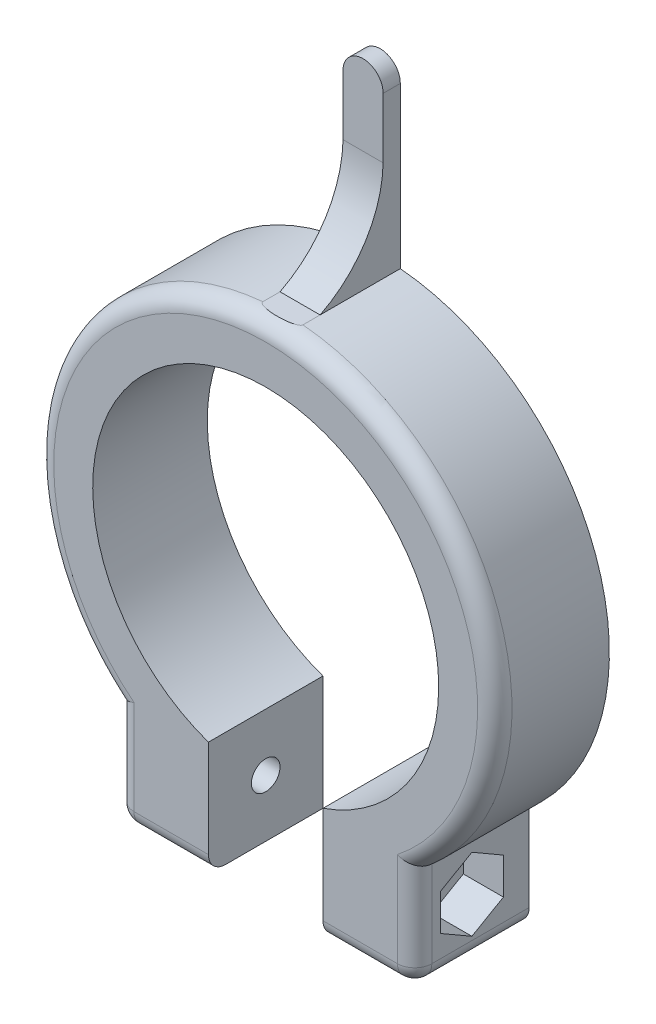
SolidWorks part; units mm, degrees
ref_plane "Front Plane" through (0, 0, 0) normal (0, 0, 1) x (1, 0, 0)
ref_plane "Top Plane" through (0, 0, 0) normal (0, 1, 0) x (1, 0, 0)
ref_plane "Right Plane" through (0, 0, 0) normal (1, 0, 0) x (0, 0, -1)
sketch "Sketch1" plane through (0, 0, 0) normal (0, 0, 1) x (1, 0, 0)
  line L0 (-5, -14.2482) -> (-5, -24.2482)
  line L1 (5, -14.2482) -> (5, -24.2482)
  line L2 (-5, -24.2482) -> (-13, -24.2482)
  line L3 (5, -24.2482) -> (13, -24.2482)
  line L4 (-13, -24.2482) -> (-13, -15.1987)
  line L5 (13, -24.2482) -> (13, -15.1987)
  line L6 (-1.75, 19.9233) -> (-1.75, 33.9233)
  line L7 (1.75, 19.9233) -> (1.75, 33.9233)
  arc A0 (5, -14.2482) -> (-5, -14.2482) centre (0, 0) ccw
  arc A1 (13, -15.1987) -> (1.75, 19.9233) centre (0, 0) ccw
  arc A2 (-1.75, 19.9233) -> (-13, -15.1987) centre (0, 0) ccw
  arc A3 (1.75, 33.9233) -> (-1.75, 33.9233) centre (0, 33.9233) ccw
  dimension "D1" = 30.2
  dimension "D2" = 40
  dimension "D13" = 1.75
  dimension "D3" = 5
  dimension "D4" = 5
  dimension "D5" = 10
  dimension "D6" = 10
  dimension "D7" = 8
  dimension "D8" = 8
  dimension "D9" = 1.75
  dimension "D10" = 1.75
  dimension "D11" = 14
  dimension "D12" = 14
extrude "Boss-Extrude1" add sketch "Sketch1" along normal blind 10
sketch "Sketch2" plane through (0, 0, 0) normal (1, 0, 0) x (0, 0, -1)
  line L0 (-10, 19.9233) -> (-7, 19.9233)
  line L1 (-10, 19.9233) -> (0, 19.9233) construction
  line L3 (-10, 35.6733) -> (-1.5, 35.6733)
  line L4 (0, 35.6733) -> (-10, 35.6733) construction
  line L5 (-10, 35.6733) -> (-10, 19.9233)
  line L6 (-1.5, 35.6733) -> (-1.5, 28.6733)
  line L7 (0, 33.9233) -> (0, 35.6733) construction
  arc A0 (-7, 19.9233) -> (-1.5, 28.6733) centre (-11.4984, 28.8544) ccw
  dimension "D4" = 10
  dimension "D1" = 1.5
  dimension "D2" = 7
  dimension "D3" = 3
extrude "Cut-Extrude1" cut sketch "Sketch2" against normal blind 2 and the other way blind 2
fillet "Fillet1" radius 1.5 3 edges at (-13, -19.7234, 10) (13, -19.7234, 10) (19.0468, 6.1009, 10)
fillet "Fillet2" radius 1.5 6 edges at (-8.25, -24.2482, 10) (-12.5607, -24.2482, 9.5607) (8.25, -24.2482, 10) (12.5607, -24.2482, 9.5607) (-13, -24.2482, 4.25) (13, -24.2482, 4.25)
sketch "Sketch3" plane through (13, 0, 0) normal (1, 0, 0) x (0, 0, -1)
  line L0 (0, -24.2482) -> (-8.5, -24.2482) construction
  line L1 (-10, -22.7482) -> (-10, -14.4914) construction
  circle A0 centre (-5, -19.2482) radius 1.25
  dimension "D1" = 2.5
  dimension "D2" = 5
  dimension "D3" = 5
extrude "Cut-Extrude2" cut sketch "Sketch3" against normal up to surface (26 mm away) up to face at (-13, -18.9734, 4.25)
sketch "Sketch4" plane through (-13, 0, 0) normal (-1, 0, 0) x (0, 0, 1)
  circle A0 centre (5, -19.2482) radius 2.75
  dimension "D1" = 5.5
extrude "Cut-Extrude3" cut sketch "Sketch4" against normal blind 3.5
sketch "Sketch5" plane through (13, 0, 0) normal (1, 0, 0) x (0, 0, -1)
  line L1 (-5, -22.4236) -> (-2.25, -20.8359)
  line L2 (-2.25, -20.8359) -> (-2.25, -17.6604)
  line L3 (-2.25, -17.6604) -> (-5, -16.0727)
  line L4 (-5, -16.0727) -> (-7.75, -17.6604)
  line L5 (-7.75, -17.6604) -> (-7.75, -20.8359)
  line L6 (-7.75, -20.8359) -> (-5, -22.4236)
  circle A0 centre (-5, -19.2482) radius 2.75 construction
  dimension "D1" = 5.5
extrude "Cut-Extrude4" cut sketch "Sketch5" against normal blind 3.5
